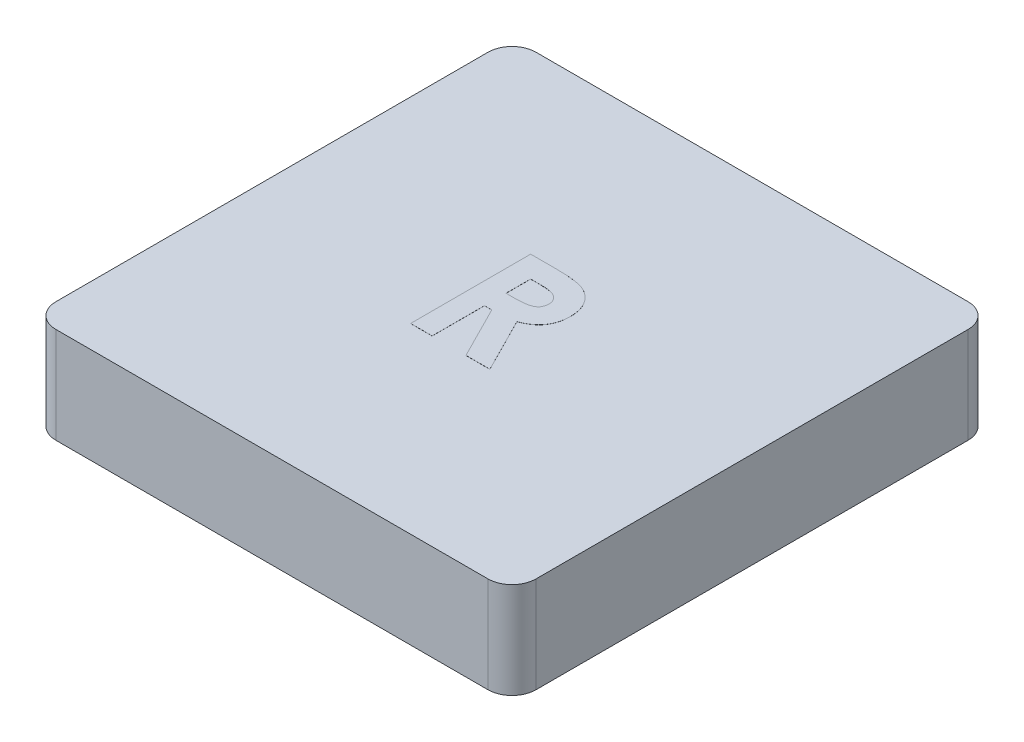
SolidWorks part; units mm, degrees
ref_plane "Front Plane" through (0, 0, 0) normal (0, 0, 1) x (1, 0, 0)
ref_plane "Top Plane" through (0, 0, 0) normal (0, 1, 0) x (1, 0, 0)
ref_plane "Right Plane" through (0, 0, 0) normal (1, 0, 0) x (0, 0, -1)
sketch "Sketch1" plane through (0, 0, 0) normal (0, 1, 0) x (1, 0, 0)
  line L0 (0, 0) -> (12.7, 0)
  line L1 (12.7, 0) -> (12.7, 12.7)
  line L2 (12.7, 12.7) -> (0, 12.7)
  line L3 (0, 12.7) -> (0, 0)
  dimension "D1" = 12.7
  dimension "D2" = 12.7
extrude "Boss-Extrude1" add sketch "Sketch1" along normal blind 2.54
fillet "Fillet1" radius 0.635 4 edges at (0, 1.27, -12.7) (12.7, 1.27, -12.7) (12.7, 1.27, 0) (0, 1.27, 0)
shell "Shell1" thickness 0.635 removed face at (6.35, 0, -6.35)
sketch "Sketch2" plane through (0, 1.905, 0) normal (0, -1, 0) x (-1, 0, 0)
  line L0 (-0.635, 6.35) -> (-12.065, 6.35) construction
  line L1 (-0.635, 12.065) -> (-0.635, 0.635) construction
  line L2 (-12.065, 0.635) -> (-12.065, 12.065) construction
  line L3 (-6.35, 0.635) -> (-6.35, 12.065) construction
  line L4 (-0.635, 0.635) -> (-12.065, 0.635) construction
  line L5 (-12.065, 12.065) -> (-0.635, 12.065) construction
  circle A0 centre (-6.35, 6.35) radius 2.54
  dimension "D1" = 5.08
extrude "Boss-Extrude2" add sketch "Sketch2" along normal up to surface (1.905 mm away) up to face at (6.35, 0, -6.35)
sketch "Sketch3" plane through (0, 2.54, 0) normal (0, 1, 0) x (1, 0, 0)
  line L0 (0, 12.065) -> (0, 0.635) construction
  line L1 (0.635, 0) -> (12.065, 0) construction
  text T0 "<b>R</b>"
  point P1 (0, 0)
  dimension "D1" = 4.826
  dimension "D2" = 4.826
extrude "Boss-Extrude3" add sketch "Sketch3" along normal blind 0.0025
